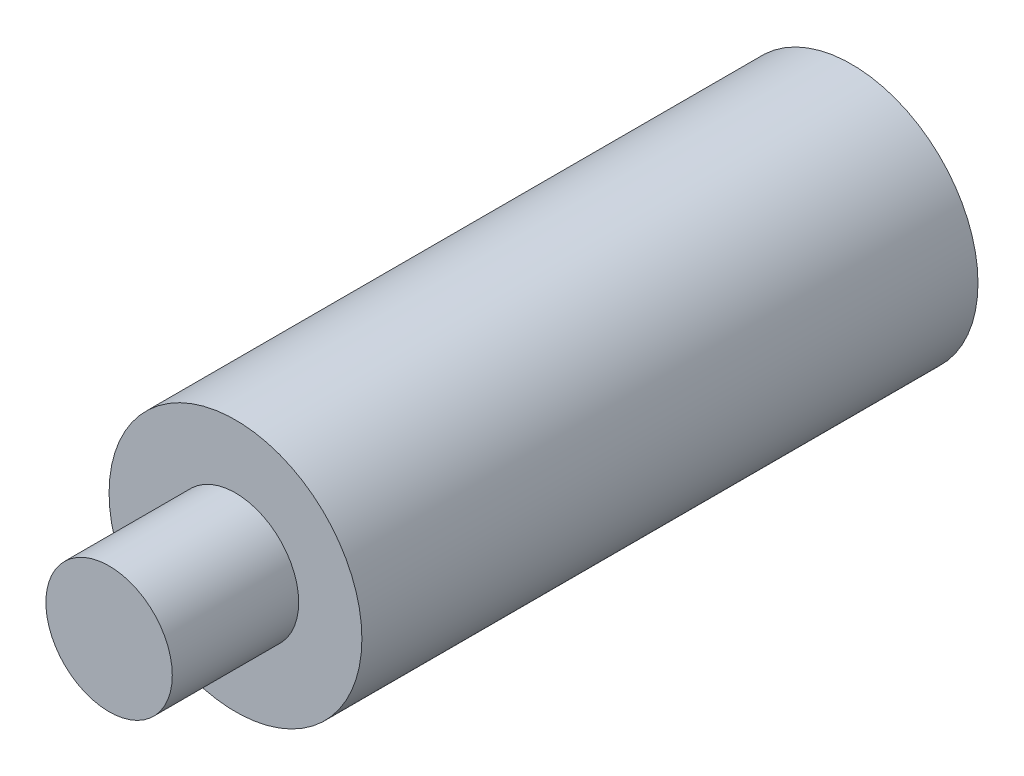
SolidWorks part; units mm, degrees
ref_plane "Front Plane" through (0, 0, 0) normal (1, 0, 0) x (0, 1, 0)
ref_plane "Top Plane" through (0, 0, 0) normal (0, 0, 1) x (0, 1, 0)
ref_plane "Right Plane" through (0, 0, 0) normal (0, 1, 0) x (-1, 0, 0)
sketch "Sketch2" plane through (0, 0, 0) normal (0, 0, 1) x (0, 1, 0)
  circle A0 centre (0, 0) radius 6.35
  dimension "D2" = 12.7
extrude "Boss-Extrude1" add sketch "Sketch2" along normal blind 30.9499
hole_wizard "Tap Drill for 1/4-20 Tap1" positions "Sketch3" profile "Sketch5" hole size "1/4-20" standard "ANSI Inch"
sketch "Sketch3" plane through (0, 0, 0) normal (0, 0, -1) x (-1, 0, 0)
  point P0 (0, 0)
sketch "Sketch5" plane through (0, 0, 0) normal (1, 0, 0) x (0, 1, 0)
  line L0 (0, 0) -> (0, 14.2338)
  line L1 (0, 14.2338) -> (2.5527, 12.7)
  line L2 (2.5527, 12.7) -> (2.5527, 0)
  line L5 (2.5527, 0) -> (0, 0)
  line L10 (0, 14.2338) -> (-2.5527, 12.7) construction
  line L11 (0, -6.35) -> (0, 107.95) construction
  dimension "Hole Dia." = 5.1054
  dimension "Hole Depth" = 12.7
  dimension "Drill Angle" = 118
sketch "Sketch6" plane through (0, 0, 30.9499) normal (0, 0, 1) x (1, 0, 0)
  circle A0 centre (0, 0) radius 3.175
  dimension "D1" = 6.35
extrude "Boss-Extrude2" add sketch "Sketch6" along normal blind 6.35
